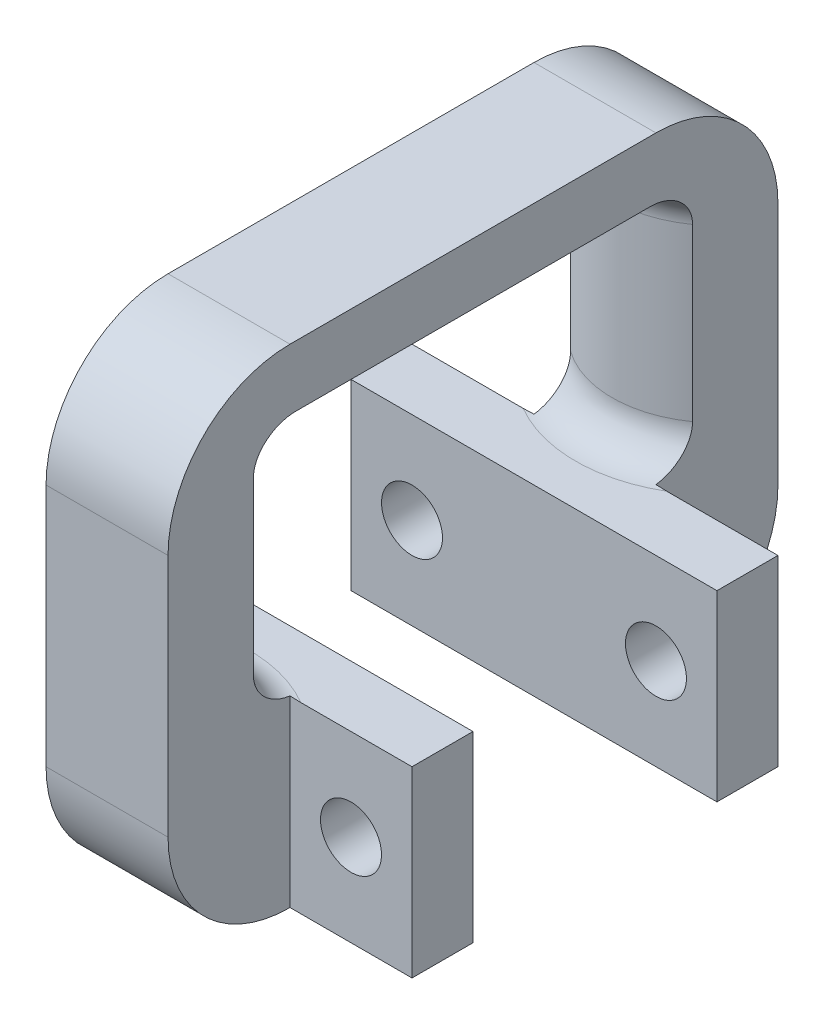
SolidWorks part; units mm, degrees
material "ABS"
ref_plane "Plan de face" through (0, 0, 0) normal (0, 0, 1) x (1, 0, 0)
ref_plane "Plan de dessus" through (0, 0, 0) normal (0, 1, 0) x (1, 0, 0)
ref_plane "Plan de droite" through (0, 0, 0) normal (1, 0, 0) x (0, 0, -1)
sketch "Esquisse1" plane through (0, 0, 0) normal (0, 0, 1) x (1, 0, 0)
  line L0 (0, -1000) -> (0, 49000) construction
  line L1 (-15, 7.5) -> (15, 7.5)
  line L2 (-15, 7.5) -> (-15, -7.5)
  line L3 (-15, -7.5) -> (15, -7.5)
  line L4 (15, 7.5) -> (15, -7.5)
  line L5 (-15, 7.5) -> (15, -7.5) construction
  line L6 (-15, -7.5) -> (15, 7.5) construction
  circle A0 centre (-10, 0) radius 2.5
  circle A1 centre (10, 0) radius 2.5
  point P0 (0, 0)
  dimension "D3" = 5
  dimension "D1" = 30
  dimension "D2" = 15
  dimension "D4" = 10
extrude "Boss.-Extru.2" add sketch "Esquisse1" along normal blind 5
sketch "Esquisse2" plane through (0, 0, 5) normal (0, 0, 1) x (1, 0, 0)
  line L0 (15, 7.5) -> (-15, 7.5) construction
  line L1 (5, -7.5) -> (-5, -7.5)
  line L2 (5, -7.5) -> (5, 7.5)
  line L3 (5, 7.5) -> (-5, 7.5)
  line L4 (-5, -7.5) -> (-5, 7.5)
  line L5 (5, -7.5) -> (-5, 7.5) construction
  line L6 (5, 7.5) -> (-5, -7.5) construction
  point P0 (0, 0)
  dimension "D1" = 10
extrude "Boss.-Extru.3" add sketch "Esquisse2" along normal blind 10
sketch "Esquisse3" plane through (0, 7.5, 0) normal (0, 1, 0) x (1, 0, 0)
  line L0 (5, -15) -> (-5, -15) construction
  line L1 (-5, -15) -> (-5, -5) construction
  line L2 (5, -15) -> (5, -5) construction
  line L3 (-5, -8) -> (-5, -15)
  line L4 (-5, -15) -> (5, -15)
  line L5 (5, -15) -> (5, -8)
  line L6 (-5, -8) -> (5, -8)
  arc A0 (-5, -8) -> (5, -8) centre (0, -15) cw
  line M4 (-5, -5) -> (-5, -15)
  line M5 (-5, -15) -> (5, -15)
  line M6 (5, -15) -> (5, -5)
  dimension "D1" = 7
extrude "Boss.-Extru.5" add sketch "Esquisse3" along normal blind 25 contours L6 M4 M5 M6 region at (0, 7.5, 11.5)
extrude "Boss.-Extru.6" add sketch "Esquisse3<4>" along normal blind 20 contours A0 L6 region at (0, 7.5, 7.3537)
sketch "Esquisse3<4>" plane through (0, 7.5, 0) normal (0, 1, 0) x (1, 0, 0) same geometry as "Esquisse3"
sketch "Esquisse4" plane through (0, 0, 8) normal (0, 0, -1) x (-1, 0, 0)
  line L1 (-5, 32.5) -> (5, 32.5)
  line L2 (-5, 32.5) -> (-5, 27.5)
  line L3 (-5, 27.5) -> (5, 27.5)
  line L4 (5, 32.5) -> (5, 27.5)
extrude "Boss.-Extru.7" add sketch "Esquisse4" along normal blind 18
fillet "Congé1" radius 10 2 edges at (0, -7.5, 15) (0, 32.5, 15)
fillet "Congé2" radius 3 2 edges at (0, 7.5, 6.3977) (0, 27.5, 6.3977)
mirror "Symétrie3" about plane through (0, 0, -10) normal (0, 0, -1) of bodies 107
